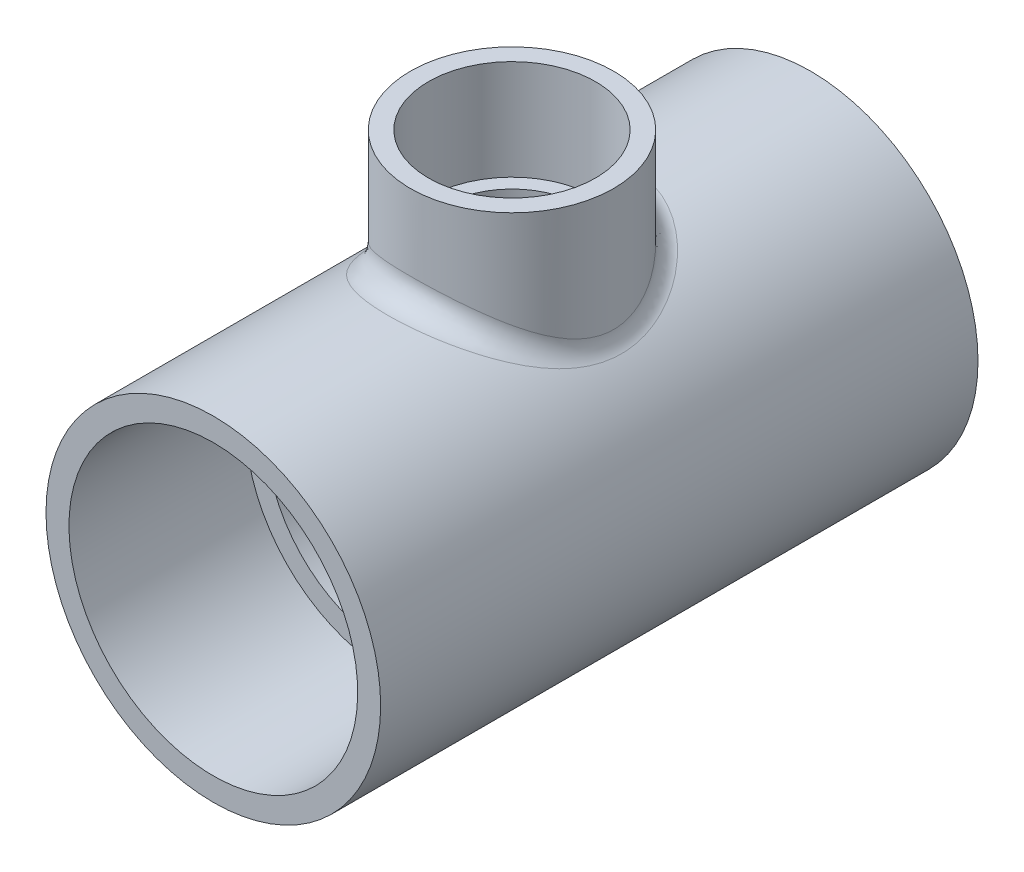
SolidWorks part; units mm, degrees
material "PVC Rigid"
ref_plane "Front Plane" through (0, 0, 0) normal (0, 0, 1) x (1, 0, 0)
ref_plane "Top Plane" through (0, 0, 0) normal (0, 1, 0) x (1, 0, 0)
ref_plane "Right Plane" through (0, 0, 0) normal (1, 0, 0) x (0, 0, -1)
sketch "Sketch1" plane through (0, 0, 0) normal (1, 0, 0) x (0, 0, -1)
  line L0 (0, 0) -> (-75.8031, 0) construction
  line L1 (0, 0) -> (75.8031, 0) construction
  line L2 (0, 0) -> (0, 73.8188) construction
  line L3 (-30.9562, -31.3563) -> (-30.9563, 31.3563) construction
  line L4 (-17.526, 42.0688) -> (17.526, 42.0688) construction
  line L5 (30.9562, -31.3563) -> (30.9562, 31.3563) construction
  line L6 (-75.8031, -42.4656) -> (-75.8031, 42.4656) construction
  line L7 (75.8031, -42.4656) -> (75.8031, 42.4656) construction
  line L8 (25.7969, 73.8188) -> (-25.7969, 73.8187) construction
  line L9 (-30.9563, 31.3563) -> (-75.8031, 31.3563) construction
  line L10 (-17.526, 42.0688) -> (-17.526, 73.8188) construction
  line L11 (30.9562, 31.3563) -> (75.8031, 31.3563) construction
  line L12 (-53.3797, -36.6395) -> (-53.3797, 36.6395) construction
  line L13 (-21.209, 57.9438) -> (21.209, 57.9438) construction
  line L14 (53.3797, -36.6395) -> (53.3797, 36.6395) construction
  point P4 (0, 0)
  point P10 (-30.9562, 0)
  point P13 (0, 42.0688)
  point P16 (30.9562, 0)
  point P19 (-75.8031, 0)
  point P22 (75.8031, 0)
  point P25 (0, 73.8188)
  point P27 (-53.3797, 31.3563)
  point P31 (-53.3797, 0)
  point P34 (0, 57.9438)
  point P37 (53.3797, 0)
  point P38 (-17.526, 57.9438)
  point P39 (53.3797, 31.3563)
  dimension "Horz Leg Length" = 75.8031
  dimension "Vert Leg Length" = 73.8188
  dimension "OAL" = 151.6062
  dimension "Horz Center to Socket" = 30.9562
  dimension "D1" = 30.9562
  dimension "Vert Center to Socket" = 42.0688
  dimension "Pipe ID_A" = 62.7126
  dimension "OD_A" = 84.9313
  dimension "For Pipe OD_A" = 73.279
  dimension "OD_B" = 51.5938
  dimension "Pipe ID_B" = 35.052
  dimension "For Pipe OD_B" = 42.418
sketch "Sketch2" plane through (0, 0, 0) normal (1, 0, 0) x (0, 0, -1)
  line L0 (-75.8031, 42.4656) -> (75.8031, 42.4656)
  line L1 (75.8031, 42.4656) -> (75.8031, 0)
  line L2 (75.8031, -42.4656) -> (75.8031, 42.4656) construction
  line L8 (-75.8031, -42.4656) -> (-75.8031, 42.4656) construction
  line L9 (-75.8031, 0) -> (-75.8031, 42.4656)
  line L10 (-75.8031, 0) -> (75.8031, 0)
revolve "Revolve1" add sketch "Sketch2" angle 360 about L0
sketch "Sketch3" plane through (0, 0, 0) normal (1, 0, 0) x (0, 0, -1)
  line L0 (0, 73.8188) -> (25.7969, 73.8188)
  line L1 (25.7969, 73.8188) -> (25.7969, 0)
  line L2 (0, 0) -> (75.8031, 0) construction
  line L3 (25.7969, 0) -> (0, 0)
  line L4 (0, 0) -> (0, 73.8188)
revolve "Revolve2" add sketch "Sketch3" angle 360 about L2
sketch "Sketch4" plane through (0, 0, 0) normal (1, 0, 0) x (0, 0, -1)
  line L0 (-75.8031, 36.6395) -> (-30.9563, 36.6395)
  line L1 (-75.8031, -42.4656) -> (-75.8031, 42.4656) construction
  line L2 (-30.9563, 36.6395) -> (-30.9563, 31.3563)
  line L3 (-30.9563, 31.3563) -> (30.9562, 31.3563)
  line L4 (30.9562, 31.3563) -> (30.9562, 36.6395)
  line L5 (30.9562, 36.6395) -> (75.8031, 36.6395)
  line L6 (75.8031, -42.4656) -> (75.8031, 42.4656) construction
  line L7 (75.8031, 36.6395) -> (75.8031, 0)
  line L8 (75.8031, 0) -> (-75.8031, 0)
  line L9 (-75.8031, 0) -> (-75.8031, 36.6395)
revolve "Cut-Revolve1" cut sketch "Sketch4" angle 360 about L8
sketch "Sketch5" plane through (0, 0, 0) normal (1, 0, 0) x (0, 0, -1)
  line L0 (0, 73.8187) -> (0, 0)
  line L1 (25.7969, 73.8188) -> (-25.7969, 73.8187) construction
  line L2 (0, 0) -> (-17.526, 0)
  line L4 (0, 0) -> (-75.8031, 0) construction
  line L5 (-17.526, 0) -> (-17.526, 42.0688)
  line L6 (-17.526, 42.0688) -> (-21.209, 42.0688)
  line L7 (-21.209, 42.0688) -> (-21.209, 73.8187)
  line L8 (-21.209, 73.8187) -> (0, 73.8187)
revolve "Cut-Revolve2" cut sketch "Sketch5" angle 360 about L0
fillet "Fillet1" radius 5.7326 1 edges at (-6.7409, 41.9272, -24.9006)
sketch "Sketch6" plane through (0, 0, 0) normal (1, 0, 0) x (0, 0, -1)
  line L0 (-75.8031, 36.6395) -> (-30.9563, 36.6395)
  line L1 (-75.8031, -42.4656) -> (-75.8031, 42.4656) construction
  line L2 (-30.9563, 36.6395) -> (-30.9563, 31.3563)
  line L3 (-30.9563, 31.3563) -> (-17.526, 31.3563)
  line L4 (-17.526, 31.3563) -> (-17.526, 42.0688)
  line L5 (-17.526, 42.0688) -> (-21.209, 42.0688)
  line L6 (-21.209, 42.0688) -> (-21.209, 73.8188)
  line L7 (25.7969, 73.8188) -> (-25.7969, 73.8188) construction
  line L8 (-30.9562, -31.3563) -> (30.9562, -31.3563)
  line L9 (30.9562, -31.3563) -> (30.9562, -36.6395)
  line L10 (30.9562, -36.6395) -> (75.8031, -36.6395)
  line L11 (75.8031, -42.4656) -> (75.8031, 42.4656) construction
  line L12 (-30.9562, -31.3563) -> (-30.9562, -36.6395)
  line L13 (-30.9562, -36.6395) -> (-75.8031, -36.6395)
  line L14 (75.8031, 36.6395) -> (30.9562, 36.6395)
  line L15 (30.9562, 36.6395) -> (30.9562, 31.3563)
  line L16 (30.9562, 31.3563) -> (17.526, 31.3563)
  line L17 (17.526, 31.3563) -> (17.526, 42.0688)
  line L18 (17.526, 42.0688) -> (21.209, 42.0688)
  line L19 (21.209, 42.0688) -> (21.209, 73.8188)
sketch "Sketch7" plane through (0, 0, 75.8031) normal (0, 0, 1) x (1, 0, 0)
  circle A0 centre (0, 0) radius 36.6395 construction
  circle A1 centre (0, 0) radius 36.6395
  point P3 (0, -36.6395)
  point P4 (36.6395, 0)
  point P5 (-36.6395, 0)
  point P6 (0, 36.6395)
other "Move Face1" flip direction yes face at (0, 73.8187, 21.209) offset 6.35 parameters "D1"=6.35
equation "\"D1@Sketch1\"=\"Horz Center to Socket@Sketch1\""
equation "\"D1@Fillet1\"=\"OD_B@Sketch1\"*0.1111111111"
